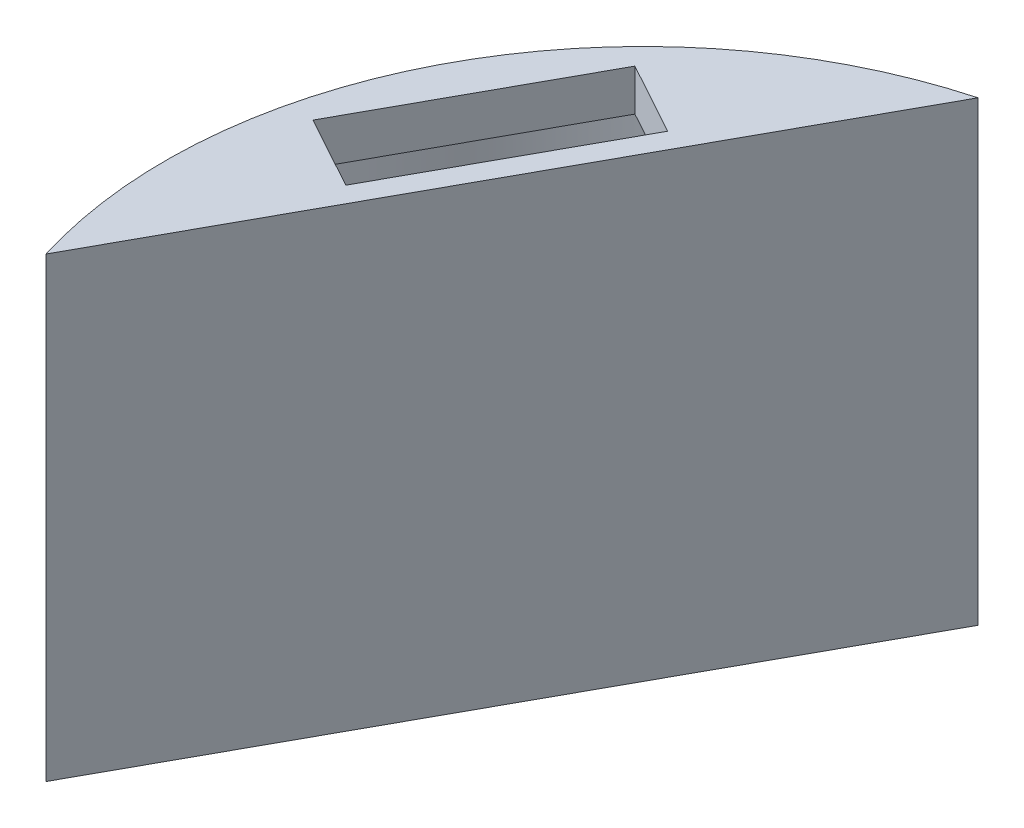
SolidWorks part; units mm, degrees
ref_plane "Front Plane" through (0, 0, 0) normal (0, 0, 1) x (1, 0, 0)
ref_plane "Top Plane" through (0, 0, 0) normal (0, 1, 0) x (1, 0, 0)
ref_plane "Right Plane" through (0, 0, 0) normal (1, 0, 0) x (0, 0, -1)
sketch "Sketch1" plane through (0, 0, 0) normal (0, 1, 0) x (1, 0, 0)
  circle A0 centre (0, 0) radius 69.85
  circle A1 centre (0, 0) radius 73.025
  dimension "D1" = 139.7
  dimension "D2" = 146.05
extrude "Boss-Extrude1" add sketch "Sketch1" along normal blind 63.5
sketch "Sketch2" plane through (0, 0, 0) normal (0, -1, 0) x (1, 0, 0)
  circle A0 centre (0, 0) radius 73.025
  dimension "D1" = 146.05
extrude "Boss-Extrude2" add sketch "Sketch2" along normal blind 6.35
sketch "Sketch3" plane through (0, 0, 0) normal (0, 1, 0) x (1, 0, 0)
  line L1 (-67.6153, -17.527) -> (-21.4092, 66.4881)
  circle A1 centre (0, 0) radius 69.85 construction
  arc A2 (-21.4092, 66.4881) -> (-67.6153, -17.527) centre (0, 0) ccw
  dimension "D1" = 50.8
extrude "Boss-Extrude3" add sketch "Sketch3" along normal blind 63.5
sketch "Sketch4" plane through (0, 63.5, 0) normal (0, 1, 0) x (1, 0, 0)
  line L0 (-25.7919, 64.9138) -> (-68.6329, -12.9827)
  line L1 (-67.6153, -17.527) -> (-21.4092, 66.4881) construction
  arc A0 (-25.7919, 64.9138) -> (-68.6329, -12.9827) centre (0, 0) ccw
  dimension "D2" = 69.85
  dimension "D1" = 88.9
extrude "Cut-Extrude2" cut sketch "Sketch4" against normal blind 57.15 from offset 6.35 offset against normal yes
ref_plane "Plane1" through (-42.2867, 0, -23.2565) normal (0.8762, 0, 0.4819) x (0.4819, 0, -0.8762)
sketch "Sketch7" plane through (0, 63.5, 0) normal (0, 1, 0) x (1, 0, 0)
  line L0 (-72.6096, -26.608) -> (-10.1714, 86.9215)
  line L1 (-10.1714, 86.9215) -> (114.9599, 65.8058)
  line L2 (114.9599, 65.8058) -> (122.5488, -33.7487)
  line L3 (122.5488, -33.7487) -> (41.0179, -93.9807)
  line L4 (41.0179, -93.9807) -> (-75.6034, -72.6768)
  line L5 (-75.6034, -72.6768) -> (-72.6096, -26.608)
  line L6 (-67.6153, -17.527) -> (-21.4092, 66.4881) construction
extrude "Cut-Extrude5" cut sketch "Sketch7" against normal blind 1016
sketch "Sketch8" plane through (0, 63.5, 0) normal (0, 1, 0) x (1, 0, 0)
  line L0 (-38.5266, 42.2924) -> (-55.9883, 10.5424)
  line L1 (-55.9883, 10.5424) -> (-67.1163, 16.6625)
  line L2 (-67.1163, 16.6625) -> (-49.6547, 48.4125)
  line L3 (-49.6547, 48.4125) -> (-38.5266, 42.2924)
  line L4 (-69.7926, -21.4859) -> (-19.2319, 70.447) construction
  dimension "D1" = 31.75
  dimension "D2" = 12.7
extrude "Cut-Extrude6" cut sketch "Sketch8" against normal blind 6.35
